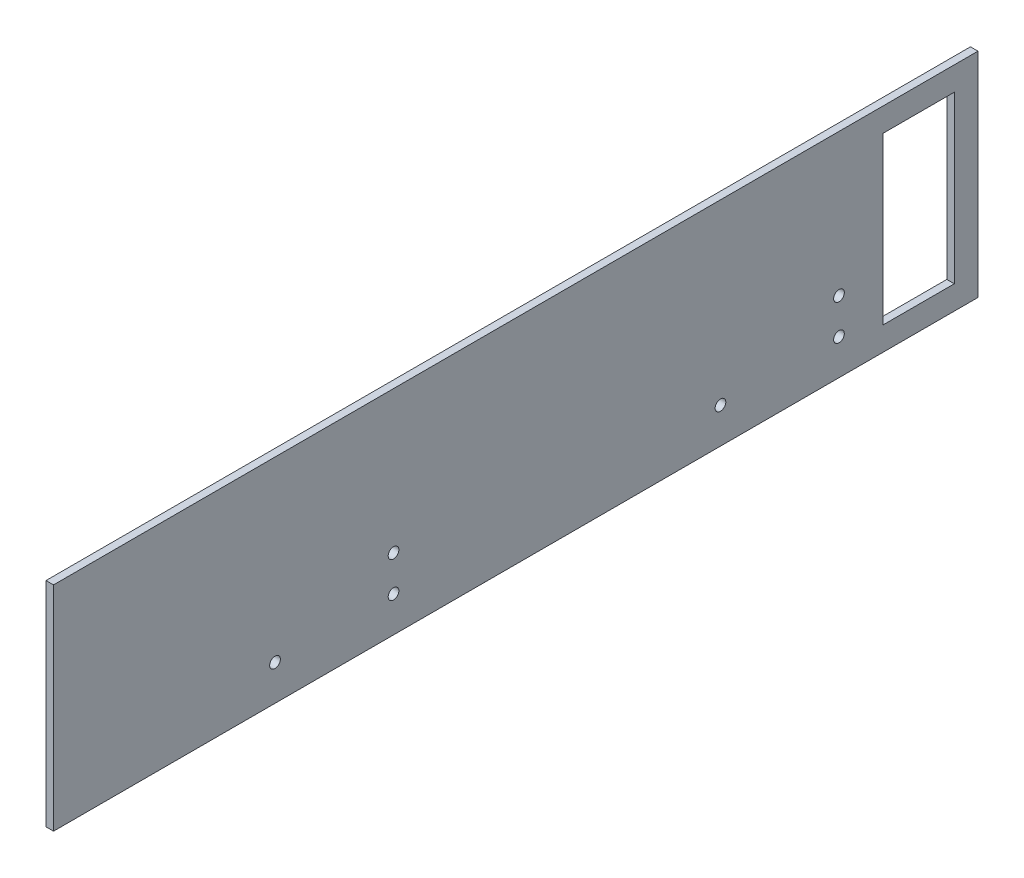
SolidWorks part; units mm, degrees
ref_plane "Front Plane" through (0, 0, 0) normal (0, 0, 1) x (1, 0, 0)
ref_plane "Top Plane" through (0, 0, 0) normal (0, 1, 0) x (1, 0, 0)
ref_plane "Right Plane" through (0, 0, 0) normal (1, 0, 0) x (0, 0, -1)
sketch "Sketch1" plane through (0, 0, 0) normal (1, 0, 0) x (0, 0, -1)
  line L1 (-195, -45) -> (195, -45)
  line L2 (-195, -45) -> (-195, 45)
  line L3 (-195, 45) -> (195, 45)
  line L4 (195, -45) -> (195, 45)
  line L5 (-195, -45) -> (195, 45) construction
  line L6 (-195, 45) -> (195, -45) construction
  point P0 (0, 0)
  dimension "D1" = 390
  dimension "D2" = 90
extrude "Boss-Extrude1" add sketch "Sketch1" along normal blind 3.175
hole_wizard "M4 Clearance Hole1" positions "Sketch2" profile "Sketch3" hole size "M4" standard "ANSI Metric"
sketch "Sketch2" plane through (3.175, 0, 0) normal (1, 0, 0) x (0, 0, -1)
  line L0 (-178.884, -45) -> (-7.9152, 0.811)
  line L1 (-195, -45) -> (195, -45) construction
  line L2 (-7.9152, 0.811) -> (-20.8561, 49.1073)
  line L3 (-20.8561, 49.1073) -> (-191.825, 3.2963)
  line L4 (-191.825, 3.2963) -> (-178.884, -45)
  line L6 (9.0311, -45) -> (180, 0.811)
  line L7 (180, 0.811) -> (167.059, 49.1073)
  line L8 (167.059, 49.1073) -> (-3.9098, 3.2963)
  line L9 (-3.9098, 3.2963) -> (9.0311, -45)
  line L11 (-141.5635, -35) -> (-141.5635, -45)
  line L13 (46.3516, -45) -> (46.3516, -35)
  line L15 (195, -45) -> (195, 45) construction
  line L17 (-195, 45) -> (-195, -45) construction
  point P30 (-101.5635, -30)
  point P32 (-51.5635, -30)
  point P34 (-51.5635, -15)
  point P36 (86.3516, -30)
  point P38 (136.3516, -30)
  point P40 (136.3516, -15)
  point P41 (-195, 3.2963)
  dimension "D1" = 177
  dimension "D2" = 50
  dimension "D3" = 15
  dimension "D4" = 3.175
  dimension "D6" = 10
  dimension "D7" = 15
  dimension "D8" = 10
  dimension "D9" = 40
  dimension "D10" = 90
  dimension "D11" = 15
  dimension "D12" = 15
  dimension "D13" = 40
  dimension "D14" = 90
  dimension "D5" = 2
sketch "Sketch3" plane through (3.175, -15, -136.3516) normal (0, 1, 0) x (0, 0, -1)
  line L0 (0, 0) -> (0, 11.4519)
  line L1 (0, 11.4519) -> (2.25, 10.1)
  line L2 (2.25, 10.1) -> (2.25, 0)
  line L5 (2.25, 0) -> (0, 0)
  line L10 (0, 11.4519) -> (-2.25, 10.1) construction
  line L11 (0, -6.35) -> (0, 107.95) construction
  dimension "Hole Dia." = 4.5
  dimension "Hole Depth" = 10.1
  dimension "Drill Angle" = 118
sketch "Sketch4" plane through (3.175, 0, 0) normal (1, 0, 0) x (0, 0, -1)
  line L0 (195, -45) -> (195, 45) construction
  line L1 (155, -35) -> (185, -35)
  line L2 (155, -35) -> (155, 35)
  line L3 (155, 35) -> (185, 35)
  line L4 (185, -35) -> (185, 35)
  line L5 (155, -35) -> (185, 35) construction
  line L6 (155, 35) -> (185, -35) construction
  point P0 (170, 0)
  dimension "D1" = 30
  dimension "D2" = 70
  dimension "D3" = 10
extrude "Cut-Extrude1" cut sketch "Sketch4" against normal through all
